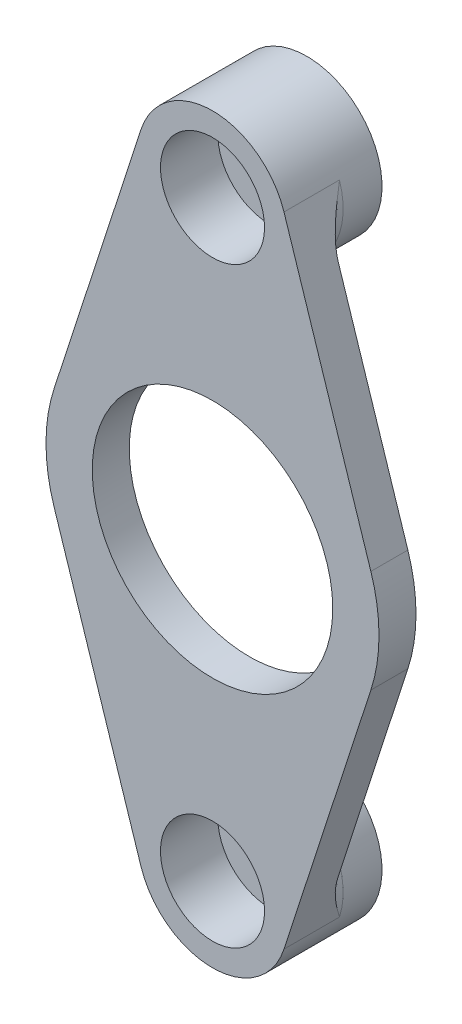
SolidWorks part; units mm, degrees
ref_plane "Front Plane" through (0, 0, 0) normal (0, 0, 1) x (1, 0, 0)
ref_plane "Top Plane" through (0, 0, 0) normal (0, 1, 0) x (1, 0, 0)
ref_plane "Right Plane" through (0, 0, 0) normal (1, 0, 0) x (0, 0, -1)
sketch "Sketch1" plane through (0, 0, 0) normal (0, 0, 1) x (1, 0, 0)
  line L0 (0, -20.32) -> (0, 20.32) construction
  line L1 (0, 0) -> (11.43, 0) construction
  line L2 (-4.9076, 21.9122) -> (-10.8721, 3.5272)
  line L3 (4.9076, 21.9122) -> (10.8721, 3.5272)
  line L4 (4.9076, -21.9122) -> (10.8721, -3.5272)
  line L5 (-4.9076, -21.9122) -> (-10.8721, -3.5272)
  circle A0 centre (0, 0) radius 8.255
  arc A1 (-10.8721, 3.5272) -> (-10.8721, -3.5272) centre (0, 0) ccw
  arc A2 (4.9076, 21.9122) -> (-4.9076, 21.9122) centre (0, 20.32) ccw
  arc A3 (4.9076, -21.9122) -> (-4.9076, -21.9122) centre (0, -20.32) cw
  arc A4 (10.8721, -3.5272) -> (10.8721, 3.5272) centre (0, 0) ccw
  circle A6 centre (0, 20.32) radius 3.5719
  circle A7 centre (0, -20.32) radius 3.5719
  dimension "D1" = 16.51
  dimension "D2" = 22.86
  dimension "D4" = 10.3187
  dimension "D5" = 7.1437
  dimension "D3" = 20.32
extrude "Boss-Extrude1" add sketch "Sketch1" along normal blind 2.54
sketch "Sketch3" plane through (0, 0, 2.54) normal (0, 0, 1) x (1, 0, 0)
  line L0 (0, 0) -> (11.43, 0) construction
  circle A0 centre (0, 20.32) radius 5.1594
  circle A1 centre (0, 20.32) radius 3.5719
  arc A2 (10.8721, -3.5272) -> (10.8721, 3.5272) centre (0, 0) ccw construction
  circle A3 centre (0, -20.32) radius 3.5719
  circle A4 centre (0, -20.32) radius 5.1594
extrude "Boss-Extrude2" add sketch "Sketch3" against normal blind 3.937
sketch "Sketch4" plane through (0, 0, -1.397) normal (0, 0, -1) x (-1, 0, 0)
  circle A0 centre (0, 20.32) radius 5.1594
  circle A1 centre (0, -20.32) radius 5.1594
extrude "Boss-Extrude3" add sketch "Sketch4" along normal blind 2.54
hole_wizard "#6 Clearance Hole1" positions "Sketch7" profile "Sketch6" hole size "#6" standard "ANSI Inch" end condition through all
sketch "Sketch7" plane through (0, 0, -1.397) normal (0, 0, 1) x (1, 0, 0)
  point P0 (0, 20.32)
  point P3 (0, -20.32)
sketch "Sketch6" plane through (0, 20.32, -1.397) normal (1, 0, 0) x (0, -1, 0)
  line L0 (0, 0) -> (0, 2.54)
  line L1 (0, 2.54) -> (1.8986, 2.54)
  line L2 (1.8986, 2.54) -> (1.8986, 0)
  line L5 (1.8986, 0) -> (0, 0)
  line L11 (0, -6.35) -> (0, 107.95) construction
  dimension "Thru Hole Dia." = 3.7973
  dimension "Thru Hole Depth" = 2.54
fillet "Fillet1" radius 1.27 2 edges at (0, -15.1606, 0) (0, 15.1606, 0)
equation "\"D5@Sketch1\"=9/32"
